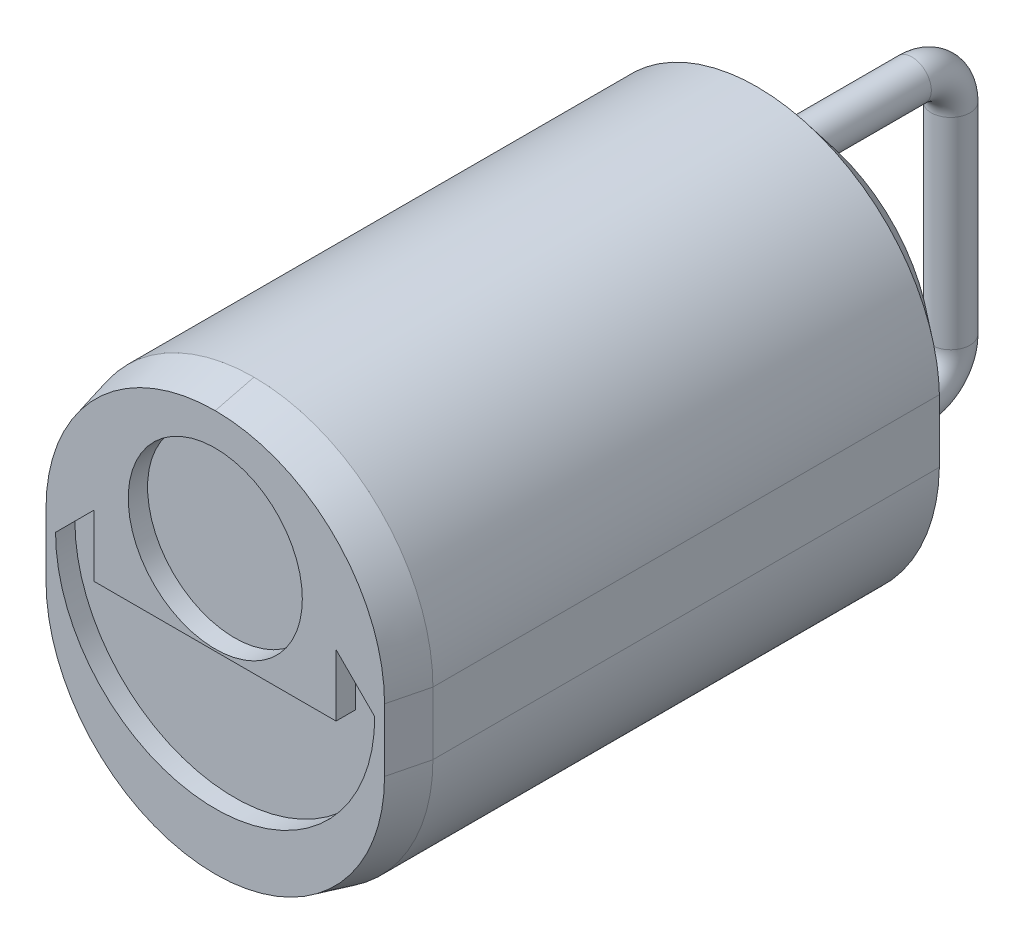
SolidWorks part; units mm, degrees
ref_plane "Front Plane" through (0, 0, 0) normal (0, 0, 1) x (1, 0, 0)
ref_plane "Top Plane" through (0, 0, 0) normal (0, 1, 0) x (1, 0, 0)
ref_plane "Right Plane" through (0, 0, 0) normal (1, 0, 0) x (0, 0, -1)
sketch "Sketch1" plane through (0, 0, 0) normal (0, 0, 1) x (1, 0, 0)
  line L2 (-58.7375, -10.3187) -> (-58.7375, 10.3188)
  line L4 (58.7375, -10.3188) -> (58.7375, 10.3187)
  line L5 (-58.7375, -10.3187) -> (58.7375, 10.3187) construction
  line L6 (-58.7375, 10.3188) -> (58.7375, -10.3188) construction
  arc A0 (-58.7375, 10.3188) -> (58.7375, 10.3187) centre (0, 10.3187) cw
  arc A1 (58.7375, -10.3188) -> (-58.7375, -10.3187) centre (0, -10.3188) cw
  point P0 (0, 0)
  point P9 (0, 69.0562)
  point P10 (0, -69.0563)
  dimension "D1" = 117.475
  dimension "D2" = 138.1125
extrude "Boss-Extrude1" add sketch "Sketch1" along normal blind 190.5
sketch "Sketch2" plane through (0, 0, 0) normal (0, 0, -1) x (-1, 0, 0)
  line L2 (-44.45, -8.89) -> (-44.45, 8.89)
  line L4 (44.45, -8.89) -> (44.45, 8.89)
  line L5 (-44.45, -8.89) -> (44.45, 8.89) construction
  line L6 (-44.45, 8.89) -> (44.45, -8.89) construction
  arc A0 (-44.45, 8.89) -> (44.45, 8.89) centre (0, 8.89) cw
  arc A2 (-44.45, -8.89) -> (44.45, -8.89) centre (0, -8.89) ccw
  point P0 (0, 0)
  point P8 (0, 53.34)
  point P9 (0, -53.34)
  dimension "D1" = 106.68
  dimension "D2" = 88.9
sketch "Sketch3" plane through (0, 0, 0) normal (1, 0, 0) x (0, 0, -1)
  line L0 (0, 53.34) -> (-12.7, 69.0563) construction
  line L1 (0, 8.89) -> (0, 53.34) construction
  line L2 (0, 69.0563) -> (-190.5, 69.0563) construction
  line L3 (0, 10.3188) -> (0, 69.0563) construction
  line L6 (-25.1271, 84.4348) -> (11.6486, 38.9248)
  line L7 (-25.1271, 84.4348) -> (23.1035, 84.4348)
  line L8 (23.1035, 84.4348) -> (11.6486, 38.9248)
  dimension "D1" = 12.7
sweep "Cut-Sweep1" cut profiles "Sketch3" path "Sketch2"
sketch "Sketch4" plane through (0, 0, 190.5) normal (0, 0, 1) x (1, 0, 0)
  line L2 (-55.5625, -10.3188) -> (-55.5625, 10.3187)
  line L4 (55.5625, -10.3188) -> (55.5625, 10.3188)
  line L5 (-55.5625, -10.3188) -> (55.5625, 10.3188) construction
  line L6 (-55.5625, 10.3187) -> (55.5625, -10.3188) construction
  arc A0 (-55.5625, 10.3187) -> (55.5625, 10.3188) centre (0, 10.3188) cw
  arc A1 (-55.5625, -10.3188) -> (55.5625, -10.3188) centre (0, -10.3188) ccw
  point P0 (0, 0)
  point P8 (0, 65.8813)
  point P9 (0, -65.8812)
  dimension "D1" = 131.7625
  dimension "D2" = 111.125
sketch "Sketch5" plane through (0, 0, 0) normal (1, 0, 0) x (0, 0, -1)
  line L0 (-190.5, 65.8813) -> (-177.8, 69.0563)
  line L1 (-190.5, 65.8813) -> (-190.5, 10.3188) construction
  line L2 (-12.7, 69.0563) -> (-190.5, 69.0563) construction
  line L3 (-190.5, 65.8813) -> (-190.5, 69.0563)
  line L4 (-190.5, 69.0563) -> (-177.8, 69.0563)
  dimension "D1" = 12.7
sweep "Cut-Sweep2" cut profiles "Sketch5" path "Sketch4"
sketch "Sketch6" plane through (0, 0, 0) normal (0, 0, -1) x (-1, 0, 0)
  circle A0 centre (0, 45.72) radius 6.35
  point P2 (0, 38.9173)
  point P5 (0, 46.3887)
  dimension "D1" = 12.7
  dimension "D2" = 7.62
sketch "Sketch7" plane through (0, 0, 0) normal (1, 0, 0) x (0, 0, -1)
  line L0 (0, 45.72) -> (38.186, 45.72)
  line L1 (0, 39.37) -> (0, 52.07) construction
  line L2 (50.886, 33.02) -> (50.886, -33.02)
  line L3 (38.186, -45.72) -> (0, -45.72)
  line L4 (0, -53.34) -> (0, -8.89) construction
  arc A0 (38.186, 45.72) -> (50.886, 33.02) centre (38.186, 33.02) cw
  arc A1 (50.886, -33.02) -> (38.186, -45.72) centre (38.186, -33.02) cw
  point P4 (50.886, 0)
  dimension "D1" = 12.7
sweep "Sweep1" add profiles "Sketch6" path "Sketch7"
sketch "Sketch8" plane through (0, 0, 190.5) normal (0, 0, 1) x (1, 0, 0)
  line L6 (39.6442, -2.54) -> (-39.7308, -2.54)
  line L7 (39.6442, 17.78) -> (39.6442, -2.54)
  line L8 (52.3442, 5.08) -> (39.6442, 17.78)
  line L9 (-39.7308, 17.78) -> (-52.4308, 5.08)
  line L10 (-39.7308, -2.54) -> (-39.7308, 17.78)
  line L11 (39.6442, -2.54) -> (-39.7308, -2.54)
  line L12 (39.6442, 17.78) -> (39.6442, -2.54)
  line L13 (52.3442, 5.08) -> (39.6442, 17.78)
  line L14 (-39.7308, 17.78) -> (-52.4308, 5.08)
  line L15 (-39.7308, -2.54) -> (-39.7308, 17.78)
  circle A1 centre (0, 26.67) radius 28.575
  circle A2 centre (0, 26.67) radius 28.575
  arc A3 (-52.4308, 5.08) -> (52.3442, 5.08) centre (-0.0433, 5.08) ccw
  arc A4 (-52.4308, 5.08) -> (52.3442, 5.08) centre (-0.0433, 5.08) ccw
  dimension "D1" = 0
  dimension "D2" = 0
extrude "Cut-Extrude1" cut sketch "Sketch8" against normal blind 6.35 contours L11 L15 L14 A4 L13 L12 | A2
equation "\"D1@Sketch2\"=4+1/5"
equation "\"D1@Sketch4\"=5+3/16"
equation "\"D2@Sketch4\"=4+3/8"
